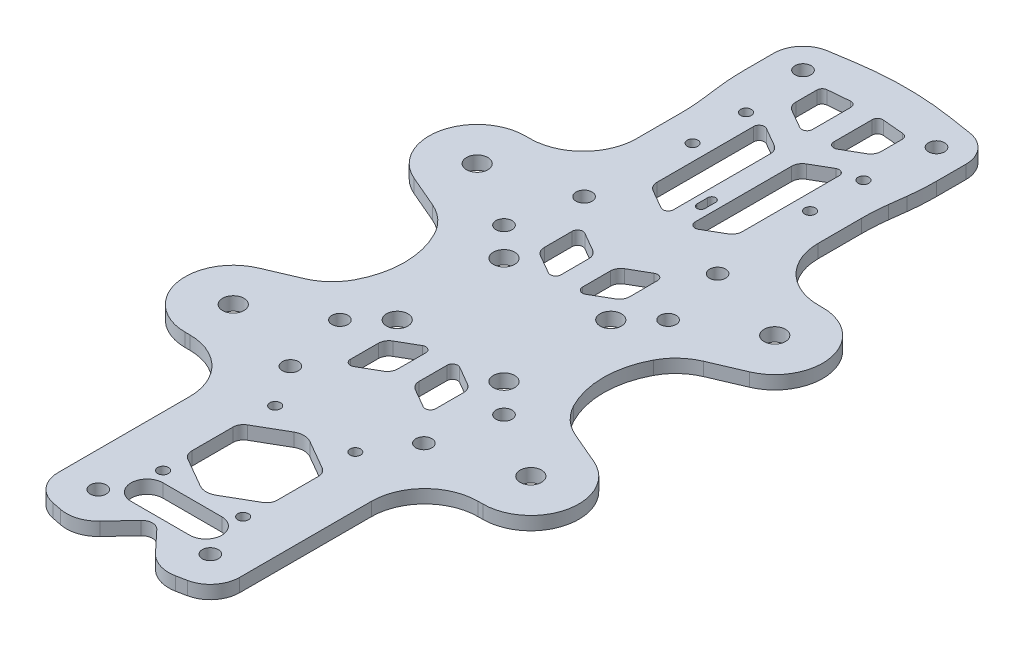
SolidWorks part; units mm, degrees
other "Markup1"
sketch "Sketch3" plane through (-36.8644, 3, -75.3176) normal (0, 1, 0) x (1, 0, 0)
material "Thornel Mat VMA"
ref_plane "Front Plane" through (0, 0, 0) normal (0, 0, 1) x (1, 0, 0)
ref_plane "Top Plane" through (0, 0, 0) normal (0, 1, 0) x (1, 0, 0)
ref_plane "Right Plane" through (0, 0, 0) normal (1, 0, 0) x (0, 0, -1)
sketch "Sketch1" plane through (0, 0, 0) normal (0, 1, 0) x (1, 0, 0)
  line L0 (7.0144, -13.8425) -> (3.5179, -11.8157)
  line L1 (-1.9927, -17.8721) -> (-1.9837, -12.6721)
  line L2 (-6.9856, 13.8181) -> (-3.4821, 11.8035)
  line L3 (2.0122, 17.9008) -> (2.0164, 12.6801)
  line L4 (2, 51.8812) -> (2, 33.7679)
  line L5 (-7, 34.9226) -> (-3.5, 32.9019)
  line L6 (3.5, 58.9019) -> (7, 60.9226)
  line L7 (-7, 60.9226) -> (-3.5, 58.9019)
  line L8 (-1.5, -37.866) -> (-7, -41.0415)
  line L9 (-6.6638, -69.1081) -> (-2.9181, -65.1127)
  line L10 (2.0164, -12.6801) -> (2.0122, -17.9008)
  line L11 (3, -19.6132) -> (6.5, -21.634)
  line L12 (8.002, -20.7686) -> (8.0113, -15.5764)
  line L13 (-3.4821, -11.8035) -> (-6.9856, -13.8181)
  line L14 (-7.9886, -15.5483) -> (-7.9977, -20.7675)
  line L15 (-6.5, -21.634) -> (-3, -19.6133)
  line L16 (-1.9837, 12.6721) -> (-1.9927, 17.8721)
  line L17 (-3, 19.6133) -> (-6.5, 21.634)
  line L18 (-7.9977, 20.7675) -> (-7.9886, 15.5483)
  line L19 (3.5179, 11.8157) -> (7.0144, 13.8425)
  line L20 (8.0113, 15.5764) -> (8.002, 20.7686)
  line L21 (6.5, 21.634) -> (3, 19.6132)
  line L22 (3.5, 32.9019) -> (7, 34.9226)
  line L23 (8, 36.6547) -> (8, 54.7679)
  line L24 (6.5, 55.634) -> (3, 53.6132)
  line L25 (-2, 33.7679) -> (-2, 51.8812)
  line L26 (-3, 53.6133) -> (-6.5, 55.634)
  line L27 (-8, 54.7679) -> (-8, 36.6546)
  line L28 (8, 62.6547) -> (8, 66.5946)
  line L29 (7.0872, 67.5908) -> (3.0872, 67.9408)
  line L30 (2, 66.9446) -> (2, 59.7679)
  line L31 (-2, 59.7679) -> (-2, 66.9446)
  line L32 (-3.0872, 67.9408) -> (-7.0872, 67.5908)
  line L33 (-8, 66.5946) -> (-8, 62.6547)
  line L34 (-8, -42.7735) -> (-8, -50.4641)
  line L35 (-7, -52.1962) -> (-1.5, -55.3716)
  line L36 (1.5, -55.3716) -> (7, -52.1962)
  line L37 (8, -50.4641) -> (8, -42.7735)
  line L38 (7, -41.0415) -> (1.5, -37.866)
  line L39 (-12.1839, -69.9325) -> (-10.3636, -70.2952)
  line L40 (-15, -41.84) -> (-15, -66.5)
  line L41 (-27.8644, -29.84) -> (-27, -29.84)
  line L42 (-24.6147, -13.8367) -> (-30.6171, -16.404)
  line L43 (-30.6171, 16.404) -> (-24.6147, 13.8367)
  line L44 (-26.9944, 29.84) -> (-27.8644, 29.84)
  line L45 (-14.9906, 49.9801) -> (-14.9944, 41.8344)
  line L46 (-15.6838, 58.0267) -> (-15.3029, 54.9969)
  line L47 (-16, 68.4976) -> (-15.9961, 62.9879)
  line L48 (-8.6637, 72.6434) -> (-13.0415, 71.9578)
  line L49 (13.0415, 71.9578) -> (8.6635, 72.6434)
  line L50 (15.9961, 62.9879) -> (15.9999, 68.4976)
  line L51 (15.3029, 54.9969) -> (15.6838, 58.0267)
  line L52 (14.9944, 41.8344) -> (14.9906, 49.98)
  line L53 (27.8644, 29.84) -> (26.9944, 29.84)
  line L54 (24.6147, 13.8367) -> (30.6171, 16.404)
  line L55 (30.6171, -16.404) -> (24.6147, -13.8367)
  line L56 (27, -29.84) -> (27.8644, -29.84)
  line L57 (15, -66.5) -> (15, -41.84)
  line L58 (10.3636, -70.2952) -> (12.1839, -69.9325)
  line L59 (2.9181, -65.1127) -> (6.6638, -69.1081)
  circle A0 centre (15.365, 15.365) radius 1.5
  circle A1 centre (15.365, -15.365) radius 1.5
  circle A2 centre (-15.365, -15.365) radius 1.5
  circle A3 centre (-15.365, 15.365) radius 1.5
  circle A4 centre (27.8644, -22.84) radius 2
  circle A5 centre (27.8644, 22.84) radius 2
  circle A6 centre (10.5, -65.5) radius 1.5
  circle A7 centre (-10, 10) radius 2
  circle A8 centre (-10, -10) radius 2
  circle A9 centre (-10.5, -65.5) radius 1.5
  circle A10 centre (-27.8644, -22.84) radius 2
  circle A11 centre (-27.8644, 22.84) radius 2
  circle A12 centre (12.5, 68.5) radius 1.5
  circle A13 centre (-12.5, 68.5) radius 1.5
  circle A14 centre (-10, -36.5) radius 1
  circle A15 centre (12.5, 27.5) radius 1.5
  circle A16 centre (-10, -56.5) radius 1
  circle A17 centre (-12.5, 27.5) radius 1.5
  circle A18 centre (12.5, -27.5) radius 1.5
  circle A19 centre (10, -36.5) radius 1
  circle A20 centre (-12.5, -27.5) radius 1.5
  circle A21 centre (10, -56.5) radius 1
  circle A22 centre (10, 10) radius 2
  circle A23 centre (10, -10) radius 2
  arc A24 (3.5179, -11.8157) -> (2.0164, -12.6801) centre (3.0164, -12.6808) ccw
  arc A25 (2.0122, -17.9008) -> (3, -19.6132) centre (3.9878, -17.9024) ccw
  arc A26 (6.5, -21.634) -> (8.002, -20.7686) centre (7.0007, -20.7668) ccw
  arc A27 (8.0113, -15.5764) -> (7.0144, -13.8425) centre (6.0113, -15.5728) ccw
  arc A28 (-1.9837, -12.6721) -> (-3.4821, -11.8035) centre (-2.9836, -12.6704) ccw
  arc A29 (-6.9856, -13.8181) -> (-7.9886, -15.5483) centre (-5.9887, -15.5518) ccw
  arc A30 (-7.9977, -20.7675) -> (-6.5, -21.634) centre (-6.9992, -20.7693) ccw
  arc A31 (-3, -19.6133) -> (-1.9927, -17.8721) centre (-4.0073, -17.8686) ccw
  arc A32 (-3.4821, 11.8035) -> (-1.9837, 12.6721) centre (-2.9836, 12.6704) ccw
  arc A33 (-1.9927, 17.8721) -> (-3, 19.6133) centre (-4.0073, 17.8686) ccw
  arc A34 (-6.5, 21.634) -> (-7.9977, 20.7675) centre (-6.9992, 20.7693) ccw
  arc A35 (-7.9886, 15.5483) -> (-6.9856, 13.8181) centre (-5.9887, 15.5518) ccw
  arc A36 (2.0164, 12.6801) -> (3.5179, 11.8157) centre (3.0164, 12.6808) ccw
  arc A37 (7.0144, 13.8425) -> (8.0113, 15.5764) centre (6.0113, 15.5728) ccw
  arc A38 (8.002, 20.7686) -> (6.5, 21.634) centre (7.0007, 20.7668) ccw
  arc A39 (3, 19.6132) -> (2.0122, 17.9008) centre (3.9878, 17.9024) ccw
  arc A40 (2, 33.7679) -> (3.5, 32.9019) centre (3, 33.7679) ccw
  arc A41 (7, 34.9226) -> (8, 36.6547) centre (6, 36.6547) ccw
  arc A42 (8, 54.7679) -> (6.5, 55.634) centre (7, 54.7679) ccw
  arc A43 (3, 53.6132) -> (2, 51.8812) centre (4, 51.8812) ccw
  arc A44 (-3.5, 32.9019) -> (-2, 33.7679) centre (-3, 33.7679) ccw
  arc A45 (-2, 51.8812) -> (-3, 53.6133) centre (-4, 51.8812) ccw
  arc A46 (-6.5, 55.634) -> (-8, 54.7679) centre (-7, 54.7679) ccw
  arc A47 (-8, 36.6546) -> (-7, 34.9226) centre (-6, 36.6546) ccw
  arc A48 (7, 60.9226) -> (8, 62.6547) centre (6, 62.6547) ccw
  arc A49 (8, 66.5946) -> (7.0872, 67.5908) centre (7, 66.5946) ccw
  arc A50 (3.0872, 67.9408) -> (2, 66.9446) centre (3, 66.9446) ccw
  arc A51 (2, 59.7679) -> (3.5, 58.9019) centre (3, 59.7679) ccw
  arc A52 (-3.5, 58.9019) -> (-2, 59.7679) centre (-3, 59.7679) ccw
  arc A53 (-2, 66.9446) -> (-3.0872, 67.9408) centre (-3, 66.9446) ccw
  arc A54 (-7.0872, 67.5908) -> (-8, 66.5946) centre (-7, 66.5946) ccw
  arc A55 (-8, 62.6547) -> (-7, 60.9226) centre (-6, 62.6547) ccw
  arc A56 (-7, -41.0415) -> (-8, -42.7735) centre (-6, -42.7735) ccw
  arc A57 (-8, -50.4641) -> (-7, -52.1962) centre (-6, -50.4641) ccw
  arc A58 (-1.5, -55.3716) -> (1.5, -55.3716) centre (0, -52.7735) ccw
  arc A59 (7, -52.1962) -> (8, -50.4641) centre (6, -50.4641) ccw
  arc A60 (8, -42.7735) -> (7, -41.0415) centre (6, -42.7735) ccw
  arc A61 (1.5, -37.866) -> (-1.5, -37.866) centre (0, -40.4641) ccw
  arc A62 (-10.3636, -70.2952) -> (-6.6638, -69.1081) centre (-9.582, -66.3723) ccw
  arc A63 (-15, -66.5) -> (-12.1839, -69.9325) centre (-11.5, -66.5) ccw
  arc A64 (-15, -41.84) -> (-27, -29.84) centre (-27, -41.84) ccw
  arc A65 (-30.6171, -16.404) -> (-27.8644, -29.84) centre (-27.8644, -22.84) ccw
  arc A66 (-24.6147, -13.8367) -> (-18.7242, -8.4106) centre (-29.3336, -2.8035) ccw
  arc A67 (-18.7242, -8.4106) -> (-18.7242, 8.4106) centre (-34.6384, 0) ccw
  arc A68 (-18.7242, 8.4106) -> (-24.6147, 13.8367) centre (-29.3336, 2.8035) ccw
  arc A69 (-27.8644, 29.84) -> (-30.6171, 16.404) centre (-27.8644, 22.84) ccw
  arc A70 (-26.9944, 29.84) -> (-14.9944, 41.8344) centre (-26.9944, 41.84) ccw
  arc A71 (-14.9906, 49.9801) -> (-15.3029, 54.9969) centre (-54.9906, 50.008) ccw
  arc A72 (-15.9961, 62.9879) -> (-15.6838, 58.0267) centre (24.0039, 63.0156) ccw
  arc A73 (-13.0415, 71.9578) -> (-16, 68.4976) centre (-12.5, 68.5) ccw
  arc A74 (8.6635, 72.6434) -> (-8.6637, 72.6434) centre (-0.0001, 17.3176) ccw
  arc A75 (15.9999, 68.4976) -> (13.0415, 71.9578) centre (12.5, 68.5) ccw
  arc A76 (15.6838, 58.0267) -> (15.9961, 62.9879) centre (-24.0039, 63.0156) ccw
  arc A77 (15.3029, 54.9969) -> (14.9906, 49.98) centre (54.9906, 50.008) ccw
  arc A78 (14.9944, 41.8344) -> (26.9944, 29.84) centre (26.9944, 41.84) ccw
  arc A79 (30.6171, 16.404) -> (27.8644, 29.84) centre (27.8644, 22.84) ccw
  arc A80 (24.6147, 13.8367) -> (18.7242, 8.4106) centre (29.3336, 2.8035) ccw
  arc A81 (18.7242, 8.4106) -> (18.7242, -8.4106) centre (34.6384, 0) ccw
  arc A82 (18.7242, -8.4106) -> (24.6147, -13.8367) centre (29.3336, -2.8035) ccw
  arc A83 (27.8644, -29.84) -> (30.6171, -16.404) centre (27.8644, -22.84) ccw
  arc A84 (27, -29.84) -> (15, -41.84) centre (27, -41.84) ccw
  arc A85 (12.1839, -69.9325) -> (15, -66.5) centre (11.5, -66.5) ccw
  arc A86 (6.6638, -69.1081) -> (10.3636, -70.2952) centre (9.582, -66.3723) ccw
  arc A87 (2.9181, -65.1127) -> (-2.9181, -65.1127) centre (0, -67.8485) ccw
sketch "Sketch2" plane through (0, 0, 0) normal (0, 1, 0) x (1, 0, 0)
  line L0 (-3.5, 32.9019) -> (3.5, 32.9019) construction
  line L5 (0, 38.9019) -> (0, 36.9019) construction
  line L7 (0.75, 38.9019) -> (0.75, 36.9019)
  line L8 (-0.75, 38.9019) -> (-0.75, 36.9019)
  line L9 (0, 0) -> (-0.0001, 75.3176) construction
  line L10 (0, 0) -> (0, -65.8485) construction
  line L11 (-18.6384, 0) -> (18.6384, 0) construction
  line L12 (-5.5, -61.3485) -> (5.5, -61.3485) construction
  line L13 (-5.5, -58.3485) -> (5.5, -58.3485)
  line L14 (-5.5, -64.3485) -> (5.5, -64.3485)
  line L15 (-14.0001, 51.3176) -> (13.9999, 51.3176) construction
  line L16 (-14.0001, 64.3176) -> (13.9999, 64.3176) construction
  line L17 (-14.0001, 64.3176) -> (-14.0001, 44.3176) construction
  line L18 (-14.0001, 44.3176) -> (13.9999, 44.3176) construction
  line L19 (13.9999, 64.3176) -> (13.9999, 44.3176) construction
  line L20 (-14.0001, 64.3176) -> (13.9999, 44.3176) construction
  line L21 (-14.0001, 44.3176) -> (13.9999, 64.3176) construction
  line L22 (-11.0001, 46.3176) -> (10.9999, 46.3176) construction
  line L513 (7, -41.0415) -> (1.5, -37.866) construction
  line L514 (-1.5, -37.866) -> (-7, -41.0415) construction
  line L515 (1.5, -55.3716) -> (7, -52.1962) construction
  line L516 (8, -50.4641) -> (8, -42.7735) construction
  line L517 (-8, -42.7735) -> (-8, -50.4641) construction
  line L518 (-7, -52.1962) -> (-1.5, -55.3716) construction
  line L519 (3, -19.6132) -> (6.5, -21.634) construction
  line L520 (7.0144, -13.8425) -> (3.5179, -11.8157) construction
  line L521 (8.002, -20.7686) -> (8.0113, -15.5764) construction
  line L522 (2.0164, -12.6801) -> (2.0122, -17.9008) construction
  line L523 (-6.5, -21.634) -> (-3, -19.6133) construction
  line L524 (-7.9886, -15.5483) -> (-7.9977, -20.7675) construction
  line L525 (-3.4821, -11.8035) -> (-6.9856, -13.8181) construction
  line L526 (-1.9927, -17.8721) -> (-1.9837, -12.6721) construction
  line L527 (3.5179, 11.8157) -> (7.0144, 13.8425) construction
  line L528 (8.0113, 15.5764) -> (8.002, 20.7686) construction
  line L529 (6.5, 21.634) -> (3, 19.6132) construction
  line L530 (-3, 19.6133) -> (-6.5, 21.634) construction
  line L531 (-7.9977, 20.7675) -> (-7.9886, 15.5483) construction
  line L532 (-1.9837, 12.6721) -> (-1.9927, 17.8721) construction
  line L533 (2.0122, 17.9008) -> (2.0164, 12.6801) construction
  line L534 (-6.9856, 13.8181) -> (-3.4821, 11.8035) construction
  line L535 (13.3509, 73.9337) -> (8.9729, 74.6193)
  line L536 (-8.9731, 74.6193) -> (-13.3509, 73.9338)
  line L537 (-18, 68.4962) -> (-17.9961, 62.9865)
  line L538 (-17.6682, 57.7773) -> (-17.2873, 54.7475)
  line L539 (17.9961, 62.9865) -> (17.9999, 68.4962)
  line L540 (17.2873, 54.7474) -> (17.6682, 57.7773)
  line L541 (-16.9906, 49.981) -> (-16.9944, 41.8353)
  line L542 (16.9944, 41.8353) -> (16.9906, 49.9814)
  line L543 (27.8644, 31.84) -> (26.9944, 31.84)
  line L544 (25.4012, 11.9979) -> (31.4036, 14.5651)
  line L545 (31.4036, -14.5651) -> (25.4012, -11.9979)
  line L546 (27, -31.84) -> (27.8644, -31.84)
  line L547 (17, -66.5) -> (17, -41.84)
  line L548 (10.7545, -72.2567) -> (12.5748, -71.894)
  line L549 (1.4591, -66.4806) -> (5.2048, -70.476)
  line L550 (-5.2048, -70.476) -> (-1.4591, -66.4806)
  line L551 (-12.5748, -71.894) -> (-10.7545, -72.2567)
  line L552 (-17, -41.84) -> (-17, -66.5)
  line L553 (-27.8644, -31.84) -> (-27, -31.84)
  line L554 (-25.4012, -11.9979) -> (-31.4036, -14.5651)
  line L555 (-31.4036, 14.5651) -> (-25.4012, 11.9979)
  line L556 (-26.9944, 31.84) -> (-27.8644, 31.84)
  line L557 (13.3509, 73.9337) -> (8.9729, 74.6193)
  line L558 (-8.9731, 74.6193) -> (-13.3509, 73.9338)
  line L559 (-18, 68.4962) -> (-17.9961, 62.9865)
  line L560 (-17.6682, 57.7773) -> (-17.2873, 54.7475)
  line L561 (17.9961, 62.9865) -> (17.9999, 68.4962)
  line L562 (17.2873, 54.7474) -> (17.6682, 57.7773)
  line L563 (-16.9906, 49.981) -> (-16.9944, 41.8353)
  line L564 (16.9944, 41.8353) -> (16.9906, 49.9814)
  line L565 (27.8644, 31.84) -> (26.9944, 31.84)
  line L566 (25.4012, 11.9979) -> (31.4036, 14.5651)
  line L567 (31.4036, -14.5651) -> (25.4012, -11.9979)
  line L568 (27, -31.84) -> (27.8644, -31.84)
  line L569 (17, -66.5) -> (17, -41.84)
  line L570 (10.7545, -72.2567) -> (12.5748, -71.894)
  line L571 (1.4591, -66.4806) -> (5.2048, -70.476)
  line L572 (-5.2048, -70.476) -> (-1.4591, -66.4806)
  line L573 (-12.5748, -71.894) -> (-10.7545, -72.2567)
  line L574 (-17, -41.84) -> (-17, -66.5)
  line L575 (-27.8644, -31.84) -> (-27, -31.84)
  line L576 (-25.4012, -11.9979) -> (-31.4036, -14.5651)
  line L577 (-31.4036, 14.5651) -> (-25.4012, 11.9979)
  line L578 (-26.9944, 31.84) -> (-27.8644, 31.84)
  line L579 (3.5, 32.9019) -> (7, 34.9226) construction
  line L580 (-7, 34.9226) -> (-3.5, 32.9019) construction
  line L581 (8, 36.6547) -> (8, 54.7679) construction
  line L582 (6.5, 55.634) -> (3, 53.6132) construction
  line L583 (-3, 53.6133) -> (-6.5, 55.634) construction
  line L584 (-2, 33.7679) -> (-2, 51.8812) construction
  line L585 (2, 51.8812) -> (2, 33.7679) construction
  line L586 (-8, 54.7679) -> (-8, 36.6546) construction
  line L587 (3.5, 58.9019) -> (7, 60.9226) construction
  line L588 (8, 62.6547) -> (8, 66.5946) construction
  line L589 (7.0872, 67.5908) -> (3.0872, 67.9408) construction
  line L590 (2, 66.9446) -> (2, 59.7679) construction
  line L591 (-7, 60.9226) -> (-3.5, 58.9019) construction
  line L592 (-2, 59.7679) -> (-2, 66.9446) construction
  line L593 (-3.0872, 67.9408) -> (-7.0872, 67.5908) construction
  line L594 (-8, 66.5946) -> (-8, 62.6547) construction
  line L595 (7, -41.0415) -> (1.5, -37.866)
  line L596 (-1.5, -37.866) -> (-7, -41.0415)
  line L597 (1.5, -55.3716) -> (7, -52.1962)
  line L598 (8, -50.4641) -> (8, -42.7735)
  line L599 (-8, -42.7735) -> (-8, -50.4641)
  line L600 (-7, -52.1962) -> (-1.5, -55.3716)
  line L601 (3, -19.6132) -> (6.5, -21.634)
  line L602 (7.0144, -13.8425) -> (3.5179, -11.8157)
  line L603 (8.002, -20.7686) -> (8.0113, -15.5764)
  line L604 (2.0164, -12.6801) -> (2.0122, -17.9008)
  line L605 (-6.5, -21.634) -> (-3, -19.6133)
  line L606 (-7.9886, -15.5483) -> (-7.9977, -20.7675)
  line L607 (-3.4821, -11.8035) -> (-6.9856, -13.8181)
  line L608 (-1.9927, -17.8721) -> (-1.9837, -12.6721)
  line L609 (3.5179, 11.8157) -> (7.0144, 13.8425)
  line L610 (8.0113, 15.5764) -> (8.002, 20.7686)
  line L611 (6.5, 21.634) -> (3, 19.6132)
  line L612 (-3, 19.6133) -> (-6.5, 21.634)
  line L613 (-7.9977, 20.7675) -> (-7.9886, 15.5483)
  line L614 (-1.9837, 12.6721) -> (-1.9927, 17.8721)
  line L615 (2.0122, 17.9008) -> (2.0164, 12.6801)
  line L616 (-6.9856, 13.8181) -> (-3.4821, 11.8035)
  line L617 (3.5, 32.9019) -> (7, 34.9226)
  line L618 (-7, 34.9226) -> (-3.5, 32.9019)
  line L619 (8, 36.6547) -> (8, 54.7679)
  line L620 (6.5, 55.634) -> (3, 53.6132)
  line L621 (-3, 53.6133) -> (-6.5, 55.634)
  line L622 (-2, 33.7679) -> (-2, 51.8812)
  line L623 (2, 51.8812) -> (2, 33.7679)
  line L624 (-8, 54.7679) -> (-8, 36.6546)
  line L625 (3.5, 58.9019) -> (7, 60.9226)
  line L626 (8, 62.6547) -> (8, 66.5946)
  line L627 (7.0872, 67.5908) -> (3.0872, 67.9408)
  line L628 (2, 66.9446) -> (2, 59.7679)
  line L629 (-7, 60.9226) -> (-3.5, 58.9019)
  line L630 (-2, 59.7679) -> (-2, 66.9446)
  line L631 (-3.0872, 67.9408) -> (-7.0872, 67.5908)
  line L632 (-8, 66.5946) -> (-8, 62.6547)
  arc A1 (0.75, 38.9019) -> (-0.75, 38.9019) centre (0, 38.9019) ccw
  arc A2 (-0.75, 36.9019) -> (0.75, 36.9019) centre (0, 36.9019) ccw
  circle A3 centre (-12.5, 68.5) radius 2.75 construction
  circle A4 centre (12.4998, 68.5) radius 2.75 construction
  circle A5 centre (-7.5, -35.3485) radius 1
  circle A6 centre (-7.5, -56.3485) radius 1
  circle A7 centre (7.5, -35.3485) radius 1
  circle A8 centre (7.5, -56.3485) radius 1
  arc A9 (-5.5, -58.3485) -> (-5.5, -64.3485) centre (-5.5, -61.3485) ccw
  arc A10 (5.5, -64.3485) -> (5.5, -58.3485) centre (5.5, -61.3485) ccw
  circle A11 centre (-10.5, -65.5) radius 2.75 construction
  circle A12 centre (10.5, -65.5) radius 2.75 construction
  circle A16 centre (-11.0001, 46.3176) radius 1
  circle A17 centre (10.9999, 46.3176) radius 1
  circle A18 centre (10.9999, 56.3176) radius 1
  circle A19 centre (-11.0001, 56.3176) radius 1
  arc A666 (8, -42.7735) -> (7, -41.0415) centre (6, -42.7735) ccw construction
  arc A667 (1.5, -37.866) -> (-1.5, -37.866) centre (0, -40.4641) ccw construction
  arc A668 (-7, -41.0415) -> (-8, -42.7735) centre (-6, -42.7735) ccw construction
  arc A669 (-8, -50.4641) -> (-7, -52.1962) centre (-6, -50.4641) ccw construction
  arc A670 (-1.5, -55.3716) -> (1.5, -55.3716) centre (0, -52.7735) ccw construction
  arc A671 (7, -52.1962) -> (8, -50.4641) centre (6, -50.4641) ccw construction
  circle A674 centre (10.5, -65.5) radius 1.5 construction
  circle A675 centre (-10.5, -65.5) radius 1.5 construction
  arc A676 (6.5, -21.634) -> (8.002, -20.7686) centre (7.0007, -20.7668) ccw construction
  arc A677 (2.0122, -17.9008) -> (3, -19.6132) centre (3.9878, -17.9024) ccw construction
  arc A678 (3.5179, -11.8157) -> (2.0164, -12.6801) centre (3.0164, -12.6808) ccw construction
  arc A679 (8.0113, -15.5764) -> (7.0144, -13.8425) centre (6.0113, -15.5728) ccw construction
  arc A680 (-3, -19.6133) -> (-1.9927, -17.8721) centre (-4.0073, -17.8686) ccw construction
  arc A681 (-7.9977, -20.7675) -> (-6.5, -21.634) centre (-6.9992, -20.7693) ccw construction
  arc A682 (-6.9856, -13.8181) -> (-7.9886, -15.5483) centre (-5.9887, -15.5518) ccw construction
  arc A683 (-1.9837, -12.6721) -> (-3.4821, -11.8035) centre (-2.9836, -12.6704) ccw construction
  circle A684 centre (10, -10) radius 2 construction
  circle A685 centre (15.365, -15.365) radius 1.5 construction
  circle A686 centre (27.8644, -22.84) radius 2 construction
  circle A687 centre (12.5, -27.5) radius 1.5 construction
  circle A690 centre (-10, -10) radius 2 construction
  circle A691 centre (-15.365, -15.365) radius 1.5 construction
  arc A692 (8.9729, 74.6193) -> (-8.9731, 74.6193) centre (-0.0001, 17.3176) ccw
  arc A693 (-13.3509, 73.9338) -> (-18, 68.4962) centre (-12.5, 68.5) ccw
  arc A694 (-17.9961, 62.9865) -> (-17.6682, 57.7773) centre (24.0039, 63.0156) ccw
  arc A695 (17.9999, 68.4962) -> (13.3509, 73.9337) centre (12.5, 68.5) ccw
  arc A696 (17.6682, 57.7773) -> (17.9961, 62.9865) centre (-24.0039, 63.0156) ccw
  arc A697 (-16.9906, 49.981) -> (-17.2873, 54.7475) centre (-54.9906, 50.008) ccw
  arc A698 (17.2873, 54.7474) -> (16.9906, 49.9814) centre (54.9906, 50.008) ccw
  arc A699 (16.9944, 41.8353) -> (26.9944, 31.84) centre (26.9944, 41.84) ccw
  arc A700 (31.4036, 14.5651) -> (27.8644, 31.84) centre (27.8644, 22.84) ccw
  arc A701 (25.4012, 11.9979) -> (20.4924, 7.4761) centre (29.3336, 2.8035) ccw
  arc A702 (20.4924, 7.4761) -> (20.4924, -7.4761) centre (34.6384, 0) ccw
  arc A703 (20.4924, -7.4761) -> (25.4012, -11.9979) centre (29.3336, -2.8035) ccw
  arc A704 (27.8644, -31.84) -> (31.4036, -14.5651) centre (27.8644, -22.84) ccw
  arc A705 (27, -31.84) -> (17, -41.84) centre (27, -41.84) ccw
  arc A706 (12.5748, -71.894) -> (17, -66.5) centre (11.5, -66.5) ccw
  arc A707 (5.2048, -70.476) -> (10.7545, -72.2567) centre (9.582, -66.3723) ccw
  arc A708 (1.4591, -66.4806) -> (-1.4591, -66.4806) centre (0, -67.8485) ccw
  arc A709 (-10.7545, -72.2567) -> (-5.2048, -70.476) centre (-9.582, -66.3723) ccw
  arc A710 (-17, -66.5) -> (-12.5748, -71.894) centre (-11.5, -66.5) ccw
  arc A711 (-17, -41.84) -> (-27, -31.84) centre (-27, -41.84) ccw
  arc A712 (-31.4036, -14.5651) -> (-27.8644, -31.84) centre (-27.8644, -22.84) ccw
  arc A713 (-25.4012, -11.9979) -> (-20.4924, -7.4761) centre (-29.3336, -2.8035) ccw
  arc A714 (-20.4924, -7.4761) -> (-20.4924, 7.4761) centre (-34.6384, 0) ccw
  arc A715 (-20.4924, 7.4761) -> (-25.4012, 11.9979) centre (-29.3336, 2.8035) ccw
  arc A716 (-27.8644, 31.84) -> (-31.4036, 14.5651) centre (-27.8644, 22.84) ccw
  arc A717 (-26.9944, 31.84) -> (-16.9944, 41.8353) centre (-26.9944, 41.84) ccw
  arc A718 (8.9729, 74.6193) -> (-8.9731, 74.6193) centre (-0.0001, 17.3176) ccw
  arc A719 (-13.3509, 73.9338) -> (-18, 68.4962) centre (-12.5, 68.5) ccw
  arc A720 (-17.9961, 62.9865) -> (-17.6682, 57.7773) centre (24.0039, 63.0156) ccw
  arc A721 (17.9999, 68.4962) -> (13.3509, 73.9337) centre (12.5, 68.5) ccw
  arc A722 (17.6682, 57.7773) -> (17.9961, 62.9865) centre (-24.0039, 63.0156) ccw
  arc A723 (-16.9906, 49.981) -> (-17.2873, 54.7475) centre (-54.9906, 50.008) ccw
  arc A724 (17.2873, 54.7474) -> (16.9906, 49.9814) centre (54.9906, 50.008) ccw
  arc A725 (16.9944, 41.8353) -> (26.9944, 31.84) centre (26.9944, 41.84) ccw
  arc A726 (31.4036, 14.5651) -> (27.8644, 31.84) centre (27.8644, 22.84) ccw
  arc A727 (25.4012, 11.9979) -> (20.4924, 7.4761) centre (29.3336, 2.8035) ccw
  arc A728 (20.4924, 7.4761) -> (20.4924, -7.4761) centre (34.6384, 0) ccw
  arc A729 (20.4924, -7.4761) -> (25.4012, -11.9979) centre (29.3336, -2.8035) ccw
  arc A730 (27.8644, -31.84) -> (31.4036, -14.5651) centre (27.8644, -22.84) ccw
  arc A731 (27, -31.84) -> (17, -41.84) centre (27, -41.84) ccw
  arc A732 (12.5748, -71.894) -> (17, -66.5) centre (11.5, -66.5) ccw
  arc A733 (5.2048, -70.476) -> (10.7545, -72.2567) centre (9.582, -66.3723) ccw
  arc A734 (1.4591, -66.4806) -> (-1.4591, -66.4806) centre (0, -67.8485) ccw
  arc A735 (-10.7545, -72.2567) -> (-5.2048, -70.476) centre (-9.582, -66.3723) ccw
  arc A736 (-17, -66.5) -> (-12.5748, -71.894) centre (-11.5, -66.5) ccw
  arc A737 (-17, -41.84) -> (-27, -31.84) centre (-27, -41.84) ccw
  arc A738 (-31.4036, -14.5651) -> (-27.8644, -31.84) centre (-27.8644, -22.84) ccw
  arc A739 (-25.4012, -11.9979) -> (-20.4924, -7.4761) centre (-29.3336, -2.8035) ccw
  arc A740 (-20.4924, -7.4761) -> (-20.4924, 7.4761) centre (-34.6384, 0) ccw
  arc A741 (-20.4924, 7.4761) -> (-25.4012, 11.9979) centre (-29.3336, 2.8035) ccw
  arc A742 (-27.8644, 31.84) -> (-31.4036, 14.5651) centre (-27.8644, 22.84) ccw
  arc A743 (-26.9944, 31.84) -> (-16.9944, 41.8353) centre (-26.9944, 41.84) ccw
  circle A744 centre (-12.5, -27.5) radius 1.5 construction
  circle A745 centre (-27.8644, -22.84) radius 2 construction
  circle A746 centre (27.8644, 22.84) radius 2 construction
  circle A747 centre (15.365, 15.365) radius 1.5 construction
  circle A748 centre (10, 10) radius 2 construction
  arc A749 (2.0164, 12.6801) -> (3.5179, 11.8157) centre (3.0164, 12.6808) ccw construction
  arc A750 (7.0144, 13.8425) -> (8.0113, 15.5764) centre (6.0113, 15.5728) ccw construction
  arc A751 (8.002, 20.7686) -> (6.5, 21.634) centre (7.0007, 20.7668) ccw construction
  arc A752 (3, 19.6132) -> (2.0122, 17.9008) centre (3.9878, 17.9024) ccw construction
  arc A753 (-1.9927, 17.8721) -> (-3, 19.6133) centre (-4.0073, 17.8686) ccw construction
  arc A754 (-6.5, 21.634) -> (-7.9977, 20.7675) centre (-6.9992, 20.7693) ccw construction
  arc A755 (-7.9886, 15.5483) -> (-6.9856, 13.8181) centre (-5.9887, 15.5518) ccw construction
  arc A756 (-3.4821, 11.8035) -> (-1.9837, 12.6721) centre (-2.9836, 12.6704) ccw construction
  circle A757 centre (-10, 10) radius 2 construction
  circle A758 centre (-15.365, 15.365) radius 1.5 construction
  circle A759 centre (-27.8644, 22.84) radius 2 construction
  circle A760 centre (-12.5, 27.5) radius 1.5 construction
  circle A761 centre (12.5, 27.5) radius 1.5 construction
  arc A762 (7, 34.9226) -> (8, 36.6547) centre (6, 36.6547) ccw construction
  arc A763 (2, 33.7679) -> (3.5, 32.9019) centre (3, 33.7679) ccw construction
  arc A764 (-8, 36.6546) -> (-7, 34.9226) centre (-6, 36.6546) ccw construction
  arc A765 (-3.5, 32.9019) -> (-2, 33.7679) centre (-3, 33.7679) ccw construction
  arc A766 (8, 54.7679) -> (6.5, 55.634) centre (7, 54.7679) ccw construction
  arc A767 (3, 53.6132) -> (2, 51.8812) centre (4, 51.8812) ccw construction
  arc A768 (-2, 51.8812) -> (-3, 53.6133) centre (-4, 51.8812) ccw construction
  arc A769 (-6.5, 55.634) -> (-8, 54.7679) centre (-7, 54.7679) ccw construction
  arc A770 (2, 59.7679) -> (3.5, 58.9019) centre (3, 59.7679) ccw construction
  arc A771 (7, 60.9226) -> (8, 62.6547) centre (6, 62.6547) ccw construction
  arc A772 (8, 66.5946) -> (7.0872, 67.5908) centre (7, 66.5946) ccw construction
  arc A773 (3.0872, 67.9408) -> (2, 66.9446) centre (3, 66.9446) ccw construction
  arc A774 (-8, 62.6547) -> (-7, 60.9226) centre (-6, 62.6547) ccw construction
  arc A775 (-3.5, 58.9019) -> (-2, 59.7679) centre (-3, 59.7679) ccw construction
  arc A776 (-2, 66.9446) -> (-3.0872, 67.9408) centre (-3, 66.9446) ccw construction
  arc A777 (-7.0872, 67.5908) -> (-8, 66.5946) centre (-7, 66.5946) ccw construction
  circle A778 centre (-12.5, 68.5) radius 1.5 construction
  circle A779 centre (12.5, 68.5) radius 1.5 construction
  arc A780 (8, -42.7735) -> (7, -41.0415) centre (6, -42.7735) ccw
  arc A781 (1.5, -37.866) -> (-1.5, -37.866) centre (0, -40.4641) ccw
  arc A782 (-7, -41.0415) -> (-8, -42.7735) centre (-6, -42.7735) ccw
  arc A783 (-8, -50.4641) -> (-7, -52.1962) centre (-6, -50.4641) ccw
  arc A784 (-1.5, -55.3716) -> (1.5, -55.3716) centre (0, -52.7735) ccw
  arc A785 (7, -52.1962) -> (8, -50.4641) centre (6, -50.4641) ccw
  circle A788 centre (10.5, -65.5) radius 1.5
  circle A789 centre (-10.5, -65.5) radius 1.5
  arc A790 (6.5, -21.634) -> (8.002, -20.7686) centre (7.0007, -20.7668) ccw
  arc A791 (2.0122, -17.9008) -> (3, -19.6132) centre (3.9878, -17.9024) ccw
  arc A792 (3.5179, -11.8157) -> (2.0164, -12.6801) centre (3.0164, -12.6808) ccw
  arc A793 (8.0113, -15.5764) -> (7.0144, -13.8425) centre (6.0113, -15.5728) ccw
  arc A794 (-3, -19.6133) -> (-1.9927, -17.8721) centre (-4.0073, -17.8686) ccw
  arc A795 (-7.9977, -20.7675) -> (-6.5, -21.634) centre (-6.9992, -20.7693) ccw
  arc A796 (-6.9856, -13.8181) -> (-7.9886, -15.5483) centre (-5.9887, -15.5518) ccw
  arc A797 (-1.9837, -12.6721) -> (-3.4821, -11.8035) centre (-2.9836, -12.6704) ccw
  circle A798 centre (10, -10) radius 2
  circle A799 centre (15.365, -15.365) radius 1.5
  circle A800 centre (27.8644, -22.84) radius 2
  circle A801 centre (12.5, -27.5) radius 1.5
  circle A804 centre (-10, -10) radius 2
  circle A805 centre (-15.365, -15.365) radius 1.5
  circle A806 centre (-12.5, -27.5) radius 1.5
  circle A807 centre (-27.8644, -22.84) radius 2
  circle A808 centre (27.8644, 22.84) radius 2
  circle A809 centre (15.365, 15.365) radius 1.5
  circle A810 centre (10, 10) radius 2
  arc A811 (2.0164, 12.6801) -> (3.5179, 11.8157) centre (3.0164, 12.6808) ccw
  arc A812 (7.0144, 13.8425) -> (8.0113, 15.5764) centre (6.0113, 15.5728) ccw
  arc A813 (8.002, 20.7686) -> (6.5, 21.634) centre (7.0007, 20.7668) ccw
  arc A814 (3, 19.6132) -> (2.0122, 17.9008) centre (3.9878, 17.9024) ccw
  arc A815 (-1.9927, 17.8721) -> (-3, 19.6133) centre (-4.0073, 17.8686) ccw
  arc A816 (-6.5, 21.634) -> (-7.9977, 20.7675) centre (-6.9992, 20.7693) ccw
  arc A817 (-7.9886, 15.5483) -> (-6.9856, 13.8181) centre (-5.9887, 15.5518) ccw
  arc A818 (-3.4821, 11.8035) -> (-1.9837, 12.6721) centre (-2.9836, 12.6704) ccw
  circle A819 centre (-10, 10) radius 2
  circle A820 centre (-15.365, 15.365) radius 1.5
  circle A821 centre (-27.8644, 22.84) radius 2
  circle A822 centre (-12.5, 27.5) radius 1.5
  circle A823 centre (12.5, 27.5) radius 1.5
  arc A824 (7, 34.9226) -> (8, 36.6547) centre (6, 36.6547) ccw
  arc A825 (2, 33.7679) -> (3.5, 32.9019) centre (3, 33.7679) ccw
  arc A826 (-8, 36.6546) -> (-7, 34.9226) centre (-6, 36.6546) ccw
  arc A827 (-3.5, 32.9019) -> (-2, 33.7679) centre (-3, 33.7679) ccw
  arc A828 (8, 54.7679) -> (6.5, 55.634) centre (7, 54.7679) ccw
  arc A829 (3, 53.6132) -> (2, 51.8812) centre (4, 51.8812) ccw
  arc A830 (-2, 51.8812) -> (-3, 53.6133) centre (-4, 51.8812) ccw
  arc A831 (-6.5, 55.634) -> (-8, 54.7679) centre (-7, 54.7679) ccw
  arc A832 (2, 59.7679) -> (3.5, 58.9019) centre (3, 59.7679) ccw
  arc A833 (7, 60.9226) -> (8, 62.6547) centre (6, 62.6547) ccw
  arc A834 (8, 66.5946) -> (7.0872, 67.5908) centre (7, 66.5946) ccw
  arc A835 (3.0872, 67.9408) -> (2, 66.9446) centre (3, 66.9446) ccw
  arc A836 (-8, 62.6547) -> (-7, 60.9226) centre (-6, 62.6547) ccw
  arc A837 (-3.5, 58.9019) -> (-2, 59.7679) centre (-3, 59.7679) ccw
  arc A838 (-2, 66.9446) -> (-3.0872, 67.9408) centre (-3, 66.9446) ccw
  arc A839 (-7.0872, 67.5908) -> (-8, 66.5946) centre (-7, 66.5946) ccw
  circle A840 centre (-12.5, 68.5) radius 1.5
  circle A841 centre (12.5, 68.5) radius 1.5
  point P26 (0, 37.9019)
  point P72 (0, 0)
  point P75 (0, 32.9019)
  point P138 (0, -61.3485)
  point P165 (-0.0001, 54.3176)
  point P190 (-0.0001, 46.3176)
  dimension "D5" = 20
  dimension "D15" = 11
  dimension "D14" = 28
  dimension "D20" = 7
  dimension "D1" = 2
extrude "Boss-Extrude1" add sketch "Sketch2" along normal blind 2.5
